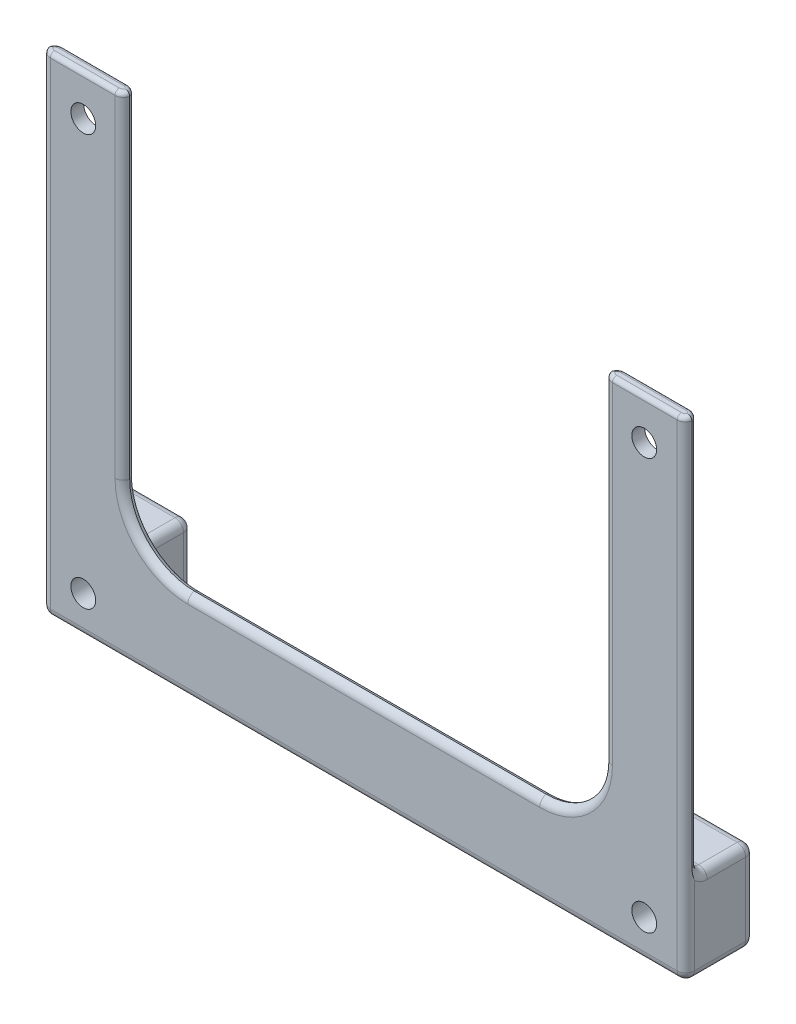
SolidWorks part; units mm, degrees
ref_plane "Plan de face" through (0, 0, 0) normal (0, 0, 1) x (1, 0, 0)
ref_plane "Plan de dessus" through (0, 0, 0) normal (0, 1, 0) x (1, 0, 0)
ref_plane "Plan de droite" through (0, 0, 0) normal (1, 0, 0) x (0, 0, -1)
sketch "Esquisse1" plane through (0, 0, 0) normal (0, 0, 1) x (1, 0, 0)
  line L0 (0.2929, 95.4142) -> (19.4142, 95.4142)
  line L1 (0.2929, 95.4142) -> (0.2929, -19)
  line L2 (19.4142, 95.4142) -> (19.4142, -19)
  line L3 (0.2929, -19) -> (19.4142, -19)
  line L5 (150.7071, 95.4142) -> (131.5858, 95.4142)
  line L6 (150.7071, 95.4142) -> (150.7071, -19)
  line L7 (131.5858, 95.4142) -> (131.5858, -19)
  line L8 (150.7071, -19) -> (131.5858, -19)
  line L10 (1, -19) -> (19, -19) construction
  line L11 (132, -19) -> (150, -19) construction
  line L12 (19.4142, -19) -> (131.5858, -19)
  line L13 (19.4142, -19) -> (19.4142, 2)
  line L14 (131.5858, -19) -> (131.5858, 2)
  line L15 (19.4142, 2) -> (131.5858, 2)
  line L16 (149, 2) -> (132, 2) construction
  arc A0 (19.7071, 94.7071) -> (18.7071, 95.7071) centre (18.7071, 94.7071) ccw construction
  arc A1 (1, 95.7071) -> (0, 94.7071) centre (1, 94.7071) ccw construction
  arc A2 (151, 94.7071) -> (150, 95.7071) centre (150, 94.7071) ccw construction
  arc A4 (132.2929, 95.7071) -> (131.2929, 94.7071) centre (132.2929, 94.7071) ccw construction
  circle A5 centre (141, -10) radius 2.9
  circle A6 centre (141, 86) radius 2.9
  circle A7 centre (10, -10) radius 2.9
  circle A8 centre (10, 86) radius 2.9
  circle A9 centre (10, -10) radius 2.9 construction
  circle A10 centre (10, 86) radius 2.9 construction
  circle A11 centre (141, -10) radius 2.9 construction
  circle A12 centre (141, 86) radius 2.9 construction
extrude "Boss.-Extru.1" add sketch "Esquisse1" along normal blind 3 contours L1 L3 L2 L0 A8 A7 | L15 L2 L12 L7 | L8 L6 L5 L7 A6 A5 region at (9.8499, 38.2122, 0) region at (75.5, -8.5, 0) region at (141.1501, 38.2122, 0)
sketch "Esquisse2" plane through (0, 0, 0) normal (0, 0, -1) x (-1, 0, 0)
  line L0 (-150.7071, -19) -> (-150.7071, 2)
  line L1 (-150.7071, -19) -> (-131.5858, -19)
  line L2 (-150.7071, 2) -> (-131.5858, 2)
  line L3 (-131.5858, -19) -> (-131.5858, 2)
  line L4 (-150.7071, 95.4142) -> (-150.7071, -19) construction
  line L5 (-0.2929, -19) -> (-19.4142, -19)
  line L6 (-0.2929, -19) -> (-0.2929, 2)
  line L7 (-19.4142, -19) -> (-19.4142, 2)
  line L8 (-0.2929, 2) -> (-19.4142, 2)
  line L9 (-0.2929, -19) -> (-150.7071, -19) construction
  circle A0 centre (-141, -10) radius 2.9
  circle A1 centre (-10, -10) radius 2.9
  circle A2 centre (-10, -10) radius 2.9 construction
  circle A3 centre (-141, -10) radius 2.9 construction
extrude "Boss.-Extru.2" add sketch "Esquisse2" along normal up to surface (13 mm away)
fillet "Congé1" radius 15 2 edges at (131.5858, 2, 1.5) (19.4142, 2, 1.5)
fillet "Congé2" radius 2 36 edges at (0.2929, 48.7071, 0) (150.7071, 48.7071, 0) (9.8536, 2, 0) (141.1464, 2, 0) (19.4142, 56.2071, 0) (23.8076, 6.3934, 0) (75.5, 2, 0) (131.5858, 56.2071, 0) (131.5858, 56.2071, 3) (19.4142, 56.2071, 3) (23.8076, 6.3934, 3) (75.5, 2, 3) (75.5, -19, 0) (9.8536, -19, -13) (0.2929, -19, -5) (19.4142, -8.5, 0) (19.4142, 2, -6.5) (141.1464, 2, -13) (150.7071, -8.5, -13) (150.7071, 2, -6.5) (131.5858, -8.5, 0) (0.2929, 38.2071, 3) (0.2929, 2, -6.5) (9.8536, 2, -13) (0.2929, -8.5, -13) (19.4142, -8.5, -13) (19.4142, -19, -6.5) (141.1464, -19, -13) (131.5858, -8.5, -13) (131.5858, 2, -6.5) (131.5858, -19, -6.5) (75.5, -19, 3) (127.1924, 6.3934, 0) (127.1924, 6.3934, 3) (150.7071, 38.2071, 3) (150.7071, -19, -5)
fillet "Congé3" radius 1 12 edges at (9.8536, 95.4142, 3) (1.0681, 95.4142, 2.5811) (1.0681, 95.4142, 0.4189) (9.8536, 95.4142, 0) (18.639, 95.4142, 0.4189) (18.639, 95.4142, 2.5811) (149.9319, 95.4142, 0.4189) (149.9319, 95.4142, 2.5811) (141.1464, 95.4142, 3) (132.361, 95.4142, 2.5811) (132.361, 95.4142, 0.4189) (141.1464, 95.4142, 0)
